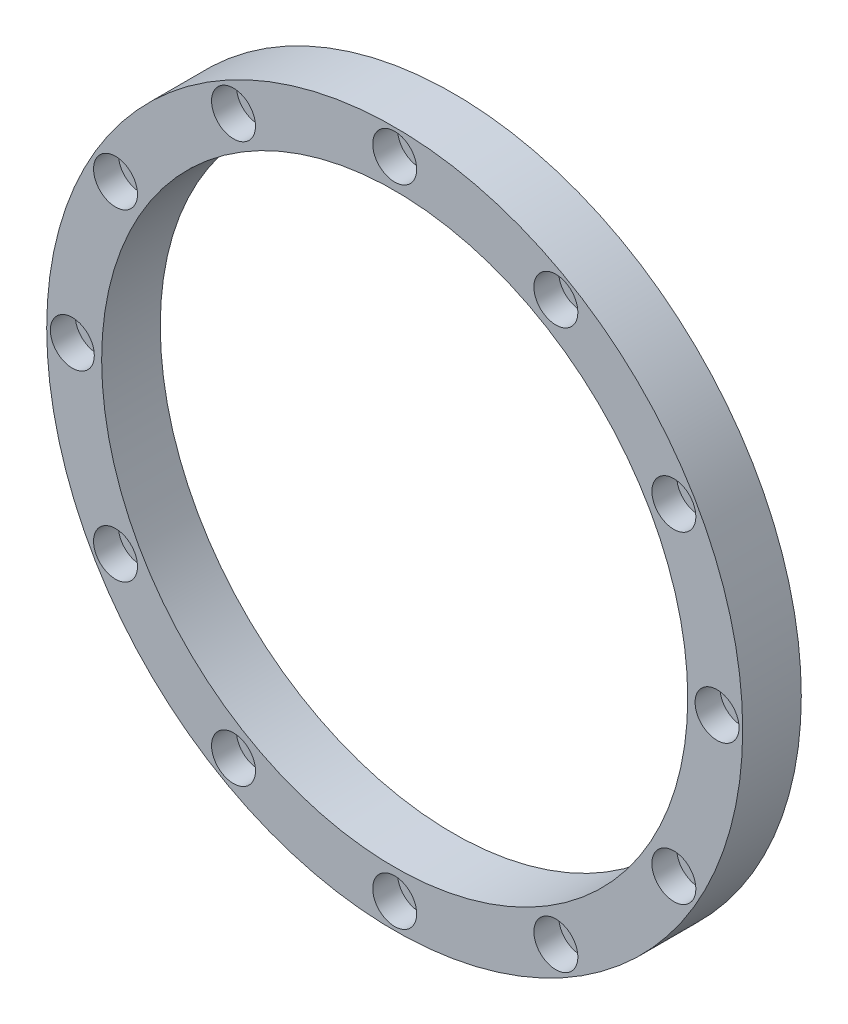
SolidWorks part; units mm, degrees
ref_plane "前视基准面" through (0, 0, 0) normal (0, 0, 1) x (1, 0, 0)
ref_plane "上视基准面" through (0, 0, 0) normal (0, 1, 0) x (1, 0, 0)
ref_plane "右视基准面" through (0, 0, 0) normal (1, 0, 0) x (0, 0, -1)
sketch "草图1" plane through (0, 0, 0) normal (0, 0, 1) x (1, 0, 0)
  circle A0 centre (0, 0) radius 47.5
  dimension "D1" = 95
extrude "凸台-拉伸1" add sketch "草图1" along normal blind 8
hole_wizard "打孔尺寸(%根据)内六角圆柱头螺钉的类型1" positions "草图3" profile "草图2" counterbore size "M3" standard "GB" end condition through all
sketch "草图3" plane through (0, 0, 8) normal (0, 0, 1) x (1, 0, 0)
  line L0 (0, 0) -> (0, 49.9167) construction
  circle A0 centre (0, 0) radius 44 construction
  point P0 (0, 44)
  dimension "D1" = 88
sketch "草图2" plane through (0, 44, 8) normal (1, 0, 0) x (0, -1, 0)
  line L0 (0, 0) -> (0, 8)
  line L1 (0, 8) -> (1.7, 8)
  line L3 (1.7, 8) -> (1.7, 3.4)
  line L4 (1.7, 3.4) -> (3, 3.4)
  line L5 (3, 3.4) -> (3, 0)
  line L7 (3, 0) -> (0, 0)
  line L11 (0, -6.35) -> (0, 107.95) construction
  dimension "通孔孔直径" = 3.4
  dimension "通孔孔深度" = 8
  dimension "柱形沉头孔直径" = 6
  dimension "柱形沉头孔深度" = 3.4
sketch "草图4" plane through (0, 0, 8) normal (0, 0, 1) x (1, 0, 0)
  circle A0 centre (0, 0) radius 40
  dimension "D1" = 80
extrude "切除-拉伸1" cut sketch "草图4" against normal through all
ref_axis "基准轴1" through (0, 0, 8) along (0, 0, -1)
pattern_circular "阵列(圆周)1" count 12 over 360 about axis through (0, 0, 8) along (0, 0, -1) of "打孔尺寸(%根据)内六角圆柱头螺钉的类型1"
